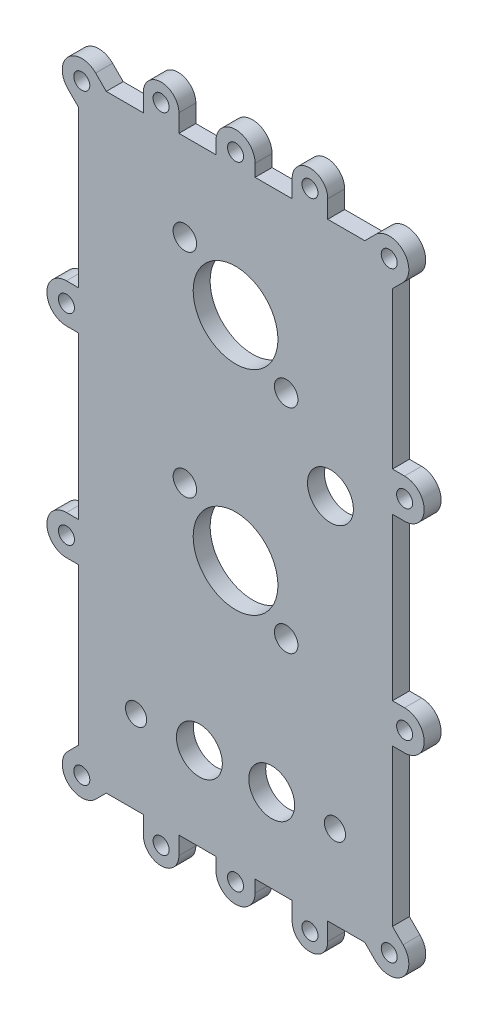
SolidWorks part; units mm, degrees
material "Acrylic (Medium-high impact)"
ref_plane "X-Y Datum" through (0, 0, 0) normal (0, 0, 1) x (1, 0, 0)
ref_plane "X-Z Datum" through (0, 0, 0) normal (0, 1, 0) x (1, 0, 0)
ref_plane "Y-Z Datum" through (0, 0, 0) normal (1, 0, 0) x (0, 0, -1)
sketch "Sketch1" plane through (0, 0, 0) normal (0, 0, 1) x (1, 0, 0)
  line L60 (50.35, 7.779) -> (19.5282, 7.779)
  line L61 (50.35, 11.1887) -> (50.35, 7.779)
  line L62 (61.35, 7.779) -> (61.35, 11.1887)
  line L63 (92.1718, 7.779) -> (61.35, 7.779)
  line L64 (95.1523, 10.7595) -> (92.1718, 7.779)
  line L65 (99.95, 0.0008) -> (102.9304, 2.9813)
  line L66 (99.95, -43.902) -> (99.95, 0.0008)
  line L67 (103.3597, -43.902) -> (99.95, -43.902)
  line L68 (99.95, -54.902) -> (103.3597, -54.902)
  line L69 (99.95, -100.29) -> (99.95, -54.902)
  line L70 (103.3597, -100.29) -> (99.95, -100.29)
  line L71 (99.95, -111.29) -> (103.3597, -111.29)
  line L72 (99.95, -155.1928) -> (99.95, -111.29)
  line L73 (102.9304, -158.1733) -> (99.95, -155.1928)
  line L74 (92.1718, -162.971) -> (95.1523, -165.9514)
  line L75 (61.35, -162.971) -> (92.1718, -162.971)
  line L76 (61.35, -166.3807) -> (61.35, -162.971)
  line L77 (50.35, -162.971) -> (50.35, -166.3807)
  line L78 (19.5282, -162.971) -> (50.35, -162.971)
  line L79 (16.5477, -165.9514) -> (19.5282, -162.971)
  line L80 (11.75, -155.1928) -> (8.7695, -158.1733)
  line L81 (11.75, -111.29) -> (11.75, -155.1928)
  line L82 (8.3403, -111.29) -> (11.75, -111.29)
  line L83 (11.75, -100.29) -> (8.3403, -100.29)
  line L84 (11.75, -54.902) -> (11.75, -100.29)
  line L85 (8.3403, -54.902) -> (11.75, -54.902)
  line L86 (11.75, -43.902) -> (8.3403, -43.902)
  line L87 (11.75, 0.0008) -> (11.75, -43.902)
  line L88 (8.7695, 2.9813) -> (11.75, 0.0008)
  line L89 (19.5282, 7.779) -> (16.5477, 10.7595)
  arc A20 (61.35, 11.1887) -> (50.35, 11.1887) centre (55.85, 11.1887) ccw
  arc A21 (102.9304, 2.9813) -> (95.1523, 10.7595) centre (99.0413, 6.8704) ccw
  arc A22 (103.3597, -54.902) -> (103.3597, -43.902) centre (103.3597, -49.402) ccw
  arc A23 (103.3597, -111.29) -> (103.3597, -100.29) centre (103.3597, -105.79) ccw
  arc A24 (95.1523, -165.9514) -> (102.9304, -158.1733) centre (99.0413, -162.0624) ccw
  arc A25 (50.35, -166.3807) -> (61.35, -166.3807) centre (55.85, -166.3807) ccw
  arc A26 (8.7695, -158.1733) -> (16.5477, -165.9514) centre (12.6586, -162.0624) ccw
  arc A27 (8.3403, -100.29) -> (8.3403, -111.29) centre (8.3403, -105.79) ccw
  arc A28 (8.3403, -43.902) -> (8.3403, -54.902) centre (8.3403, -49.402) ccw
  arc A29 (16.5477, 10.7595) -> (8.7695, 2.9813) centre (12.6586, 6.8704) ccw
extrude "Boss-Extrude1" add sketch "Sketch1" against normal blind 4.7625
hole_wizard "M4 Clearance Hole1" positions "Sketch2" profile "Sketch3" hole size "M4" standard "ANSI Metric" end condition through all
sketch "Sketch2" plane through (0, 0, -4.7625) normal (0, 0, -1) x (-1, 0, 0)
  point P0 (-12.6586, -162.0624)
  point P2 (-55.85, -166.3807)
  point P4 (-99.0413, -162.0624)
  point P6 (-103.3597, -105.79)
  point P8 (-103.3597, -49.402)
  point P10 (-99.0413, 6.8704)
  point P14 (-12.6586, 6.8704)
  point P16 (-8.3403, -49.402)
  point P18 (-8.3403, -105.79)
  point P22 (-55.85, 11.1887)
sketch "Sketch3" plane through (12.6586, -162.0624, -4.7625) normal (1, 0, 0) x (0, 1, 0)
  line L0 (0, 0) -> (0, 4.7625)
  line L1 (0, 4.7625) -> (2.25, 4.7625)
  line L2 (2.25, 4.7625) -> (2.25, 0)
  line L5 (2.25, 0) -> (0, 0)
  line L11 (0, -6.35) -> (0, 107.95) construction
  dimension "Thru Hole Dia." = 4.5
  dimension "Thru Hole Depth" = 4.7625
sketch "Sketch4" plane through (0, 0, -4.7625) normal (0, 0, -1) x (-1, 0, 0)
  line L8 (-93.95, -3.555) -> (-93.95, -119.546)
  line L9 (-93.95, -119.546) -> (-17.75, -119.546)
  line L10 (-17.75, -119.546) -> (-17.75, -3.555)
  line L11 (-23.084, 1.779) -> (-88.616, 1.779)
  line L16 (-95.5403, -3.555) -> (-95.5403, -151.637)
  line L17 (-88.616, -158.5613) -> (-23.084, -158.5613)
  line L18 (-16.1597, -151.637) -> (-16.1597, -3.555)
  line L19 (-23.084, 3.3693) -> (-88.616, 3.3693)
  line L24 (-93.95, -122.046) -> (-93.95, -151.637)
  line L25 (-17.75, -122.046) -> (-93.95, -122.046)
  line L26 (-17.75, -151.637) -> (-17.75, -122.046)
  line L27 (-88.616, -156.971) -> (-23.084, -156.971)
  circle A0 centre (-41.6161, -16.6659) radius 3.3
  circle A1 centre (-70.0839, -40.3003) radius 3.3
  circle A2 centre (-27.91, -139.5085) radius 2.9766
  circle A3 centre (-41.6161, -76.4667) radius 3.3
  circle A4 centre (-83.79, -139.5085) radius 2.9766
  circle A5 centre (-70.0839, -100.1011) radius 3.3
  arc A8 (-17.75, -3.555) -> (-23.084, 1.779) centre (-23.084, -3.555) ccw
  arc A9 (-88.616, 1.779) -> (-93.95, -3.555) centre (-88.616, -3.555) ccw
  circle A14 centre (-66.01, -139.5085) radius 6.445
  arc A16 (-95.5403, -151.637) -> (-88.616, -158.5613) centre (-88.616, -151.637) ccw
  arc A17 (-23.084, -158.5613) -> (-16.1597, -151.637) centre (-23.084, -151.637) ccw
  arc A18 (-16.1597, -3.555) -> (-23.084, 3.3693) centre (-23.084, -3.555) ccw
  arc A19 (-88.616, 3.3693) -> (-95.5403, -3.555) centre (-88.616, -3.555) ccw
  arc A22 (-23.084, -156.971) -> (-17.75, -151.637) centre (-23.084, -151.637) ccw
  arc A23 (-93.95, -151.637) -> (-88.616, -156.971) centre (-88.616, -151.637) ccw
  circle A32 centre (-82.52, -59.221) radius 6.445
  circle A34 centre (-45.69, -139.5085) radius 6.445
  circle A36 centre (-55.85, -88.2839) radius 11.9
  circle A38 centre (-55.85, -28.4831) radius 11.9
  dimension "D1" = 6.6
  dimension "D2" = 12.89
  dimension "D3" = 5.9531
  dimension "D4" = 23.8
  dimension "D5" = 12.89
  dimension "D6" = 55.88
extrude "Cut-Extrude1" cut sketch "Sketch4" against normal blind 4.7625 contours A38 | A32 | A36 | A2 | A34 | A14 | A4 | A0 | A1 | A3 | A5 region at (41.6161, -16.6659, -4.7625) region at (70.0839, -40.3003, -4.7625) region at (27.91, -139.5085, -4.7625) region at (41.6161, -76.4667, -4.7625) region at (83.79, -139.5085, -4.7625) region at (70.0839, -100.1011, -4.7625) region at (66.01, -139.5085, -4.7625) region at (82.52, -59.221, -4.7625) region at (45.69, -139.5085, -4.7625) region at (55.85, -88.2839, -4.7625) region at (55.85, -28.4831, -4.7625)
sketch "Sketch5" plane through (0, 0, -6.35) normal (0, 0, -1) x (-1, 0, 0)
  line L0 (-99.95, -77.596) -> (-104.95, -77.596) construction
  line L1 (-99.95, -100.29) -> (-99.95, -54.902) construction
  line L2 (-34.9391, 7.779) -> (-34.9391, 12.779) construction
  line L3 (-50.35, 7.779) -> (-19.5282, 7.779) construction
  line L4 (-76.7609, -162.971) -> (-76.7609, -167.971) construction
  line L5 (-29.9391, 12.779) -> (-29.9391, 7.779)
  line L6 (-61.35, -162.971) -> (-92.1718, -162.971) construction
  line L7 (-104.95, -72.596) -> (-99.95, -72.596)
  line L8 (-104.95, -82.596) -> (-99.95, -82.596)
  line L9 (-81.7609, -167.971) -> (-81.7609, -162.971)
  line L10 (-71.7609, -167.971) -> (-71.7609, -162.971)
  line L11 (-29.9391, 12.779) -> (-29.9391, 7.779)
  line L12 (-39.9391, 12.779) -> (-39.9391, 7.779)
  line L13 (-81.7609, -162.971) -> (-71.7609, -162.971)
  line L14 (-99.95, -82.596) -> (-99.95, -72.596)
  line L15 (-39.9391, 7.779) -> (-29.9391, 7.779)
  line L16 (-28.3269, -167.971) -> (-28.3269, -162.3607)
  line L17 (-55.0439, -178.7796) -> (-55.0439, -155.8273) construction
  line L19 (-28.3269, -162.3607) -> (-38.3269, -162.3607)
  line L20 (-38.3269, -167.971) -> (-38.3269, -162.3607)
  line L21 (-39.9391, 12.779) -> (-39.9391, 7.779)
  line L22 (-29.9391, 12.779) -> (-29.9391, 7.779)
  line L23 (-29.9391, 12.779) -> (-29.9391, 7.779)
  line L24 (-39.9391, 12.779) -> (-39.9391, 7.779)
  line L25 (-39.9391, 12.779) -> (-39.9391, 7.779)
  line L26 (-29.9391, 12.779) -> (-29.9391, 7.779)
  line L27 (-39.9391, 12.779) -> (-39.9391, 7.779)
  line L29 (-70.0711, 12.779) -> (-70.0711, 7.3696)
  line L30 (-70.0711, 7.3696) -> (-80.0711, 7.3696)
  line L31 (-80.0711, 12.779) -> (-80.0711, 7.3696)
  circle A1 centre (-103.3597, -105.79) radius 2.25
  circle A2 centre (-104.95, -77.596) radius 2.25 construction
  circle A3 centre (-34.9391, 12.779) radius 2.25 construction
  circle A4 centre (-76.7609, -167.971) radius 2.25 construction
  circle A5 centre (-104.95, -77.596) radius 4 construction
  circle A6 centre (-104.95, -77.596) radius 5
  circle A7 centre (-76.7609, -167.971) radius 5
  circle A8 centre (-34.9391, 12.779) radius 5
  arc A11 (-80.0711, 12.779) -> (-70.0711, 12.779) centre (-75.0711, 12.779) cw
  arc A12 (-28.3269, -167.971) -> (-38.3269, -167.971) centre (-33.3269, -167.971) cw
  circle A14 centre (-75.0711, 12.779) radius 2.25
  circle A15 centre (-33.3269, -167.971) radius 2.25
  dimension "D1" = 4.5
  dimension "D2" = 4.5
  dimension "D4" = 8
  dimension "D5" = 10
  dimension "D3" = 5
sketch "Sketch6" plane through (0, 0, 0) normal (0, 0, 1) x (1, 0, 0)
  line L0 (39.9391, 12.779) -> (39.9391, 7.779) construction
  line L1 (39.9391, 7.779) -> (29.9391, 7.779) construction
  line L2 (29.9391, 12.779) -> (29.9391, 7.779) construction
  line L3 (81.7609, -167.971) -> (81.7609, -162.971) construction
  line L4 (81.7609, -162.971) -> (71.7609, -162.971) construction
  line L5 (71.7609, -167.971) -> (71.7609, -162.971) construction
  line L9 (39.9391, 12.779) -> (39.9391, 7.779)
  line L10 (39.9391, 7.779) -> (29.9391, 7.779)
  line L11 (29.9391, 12.779) -> (29.9391, 7.779)
  line L12 (81.7609, -167.971) -> (81.7609, -162.971)
  line L13 (81.7609, -162.971) -> (71.7609, -162.971)
  line L14 (71.7609, -167.971) -> (71.7609, -162.971)
  circle A1 centre (103.3597, -105.79) radius 2.25
  circle A2 centre (103.3597, -105.79) radius 2.25
  circle A3 centre (34.9391, 12.779) radius 5
  circle A4 centre (34.9391, 12.779) radius 5
  circle A5 centre (76.7609, -167.971) radius 5
  circle A6 centre (76.7609, -167.971) radius 5
  dimension "D1" = 0
  dimension "D2" = 0
  dimension "D3" = 0
extrude "Boss-Extrude3" add sketch "Sketch6" against normal blind 4.7625 contours A6 L12 L13 L14 | A4 L11 L10 L9 | A4 | A4 L10 L9 | A6 L13 L14 | A6 region at (34.9391, 12.779, 0) region at (38.8222, 8.8959, 0) region at (31.0559, 8.8959, 0) region at (80.644, -164.0878, 0) region at (72.8777, -164.0878, 0)
hole_wizard "M4 Clearance Hole2" positions "Sketch8" profile "Sketch9" hole size "M4" standard "ANSI Metric" end condition through all
sketch "Sketch8" plane through (0, 0, 0) normal (0, 0, 1) x (1, 0, 0)
  point P11 (34.9391, 12.779)
  point P15 (76.7609, -167.971)
sketch "Sketch9" plane through (34.9391, 12.779, 0) normal (1, 0, 0) x (0, -1, 0)
  line L0 (0, 0) -> (0, 4.7625)
  line L1 (0, 4.7625) -> (2.25, 4.7625)
  line L2 (2.25, 4.7625) -> (2.25, 0)
  line L5 (2.25, 0) -> (0, 0)
  line L11 (0, -6.35) -> (0, 107.95) construction
  dimension "Thru Hole Dia." = 4.5
  dimension "Thru Hole Depth" = 4.7625
ref_plane "Plane1" through (55.85, 0, 0) normal (-1, 0, 0) x (0, 0, 1)
mirror "Mirror1" about plane through (55.85, 0, 0) normal (-1, 0, 0) of "M4 Clearance Hole2", "Boss-Extrude3"
